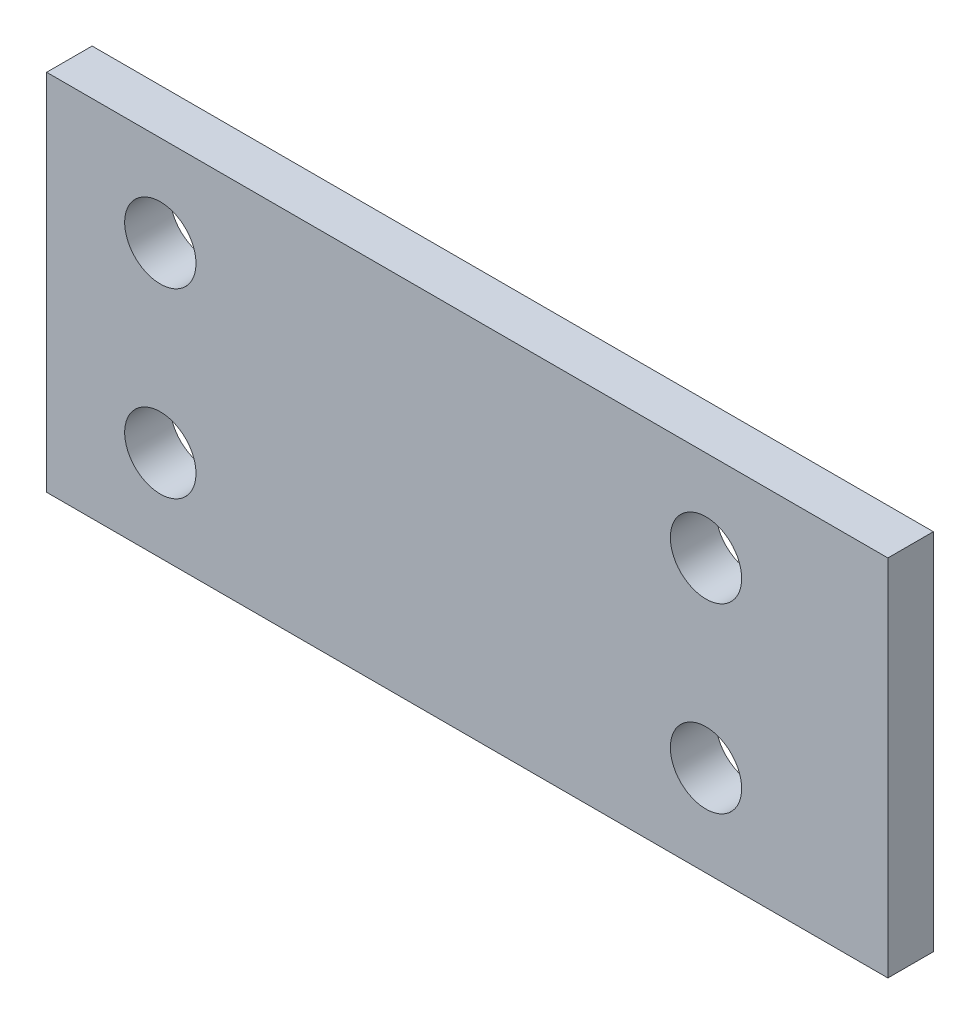
SolidWorks part; units mm, degrees
ref_plane "Front Plane" through (0, 0, 0) normal (0, 0, 1) x (1, 0, 0)
ref_plane "Top Plane" through (0, 0, 0) normal (0, 1, 0) x (1, 0, 0)
ref_plane "Right Plane" through (0, 0, 0) normal (1, 0, 0) x (0, 0, -1)
sketch "Sketch1" plane through (0, 0, 0) normal (0, 0, 1) x (1, 0, 0)
  line L1 (-29.3687, -12.7) -> (29.3687, -12.7)
  line L2 (-29.3687, -12.7) -> (-29.3687, 12.7)
  line L3 (-29.3687, 12.7) -> (29.3687, 12.7)
  line L4 (29.3687, -12.7) -> (29.3687, 12.7)
  line L5 (-29.3687, -12.7) -> (29.3687, 12.7) construction
  line L6 (-29.3687, 12.7) -> (29.3687, -12.7) construction
  circle A0 centre (-21.4312, -6.35) radius 2.4892
  circle A1 centre (16.6688, -6.35) radius 2.4892
  circle A2 centre (-21.4312, 6.35) radius 2.4892
  circle A3 centre (16.6688, 6.35) radius 2.4892
  point P0 (0, 0)
  point P13 (0, 0)
  point P16 (0, 0)
  dimension "D4" = 4.9784
  dimension "D6" = 12.7
  dimension "D7" = 6.35
  dimension "D1" = 58.7375
  dimension "D2" = 25.4
  dimension "D3" = 7.9375
  dimension "D5" = 12.7
extrude "Boss-Extrude1" add sketch "Sketch1" along normal mid plane 3.175
